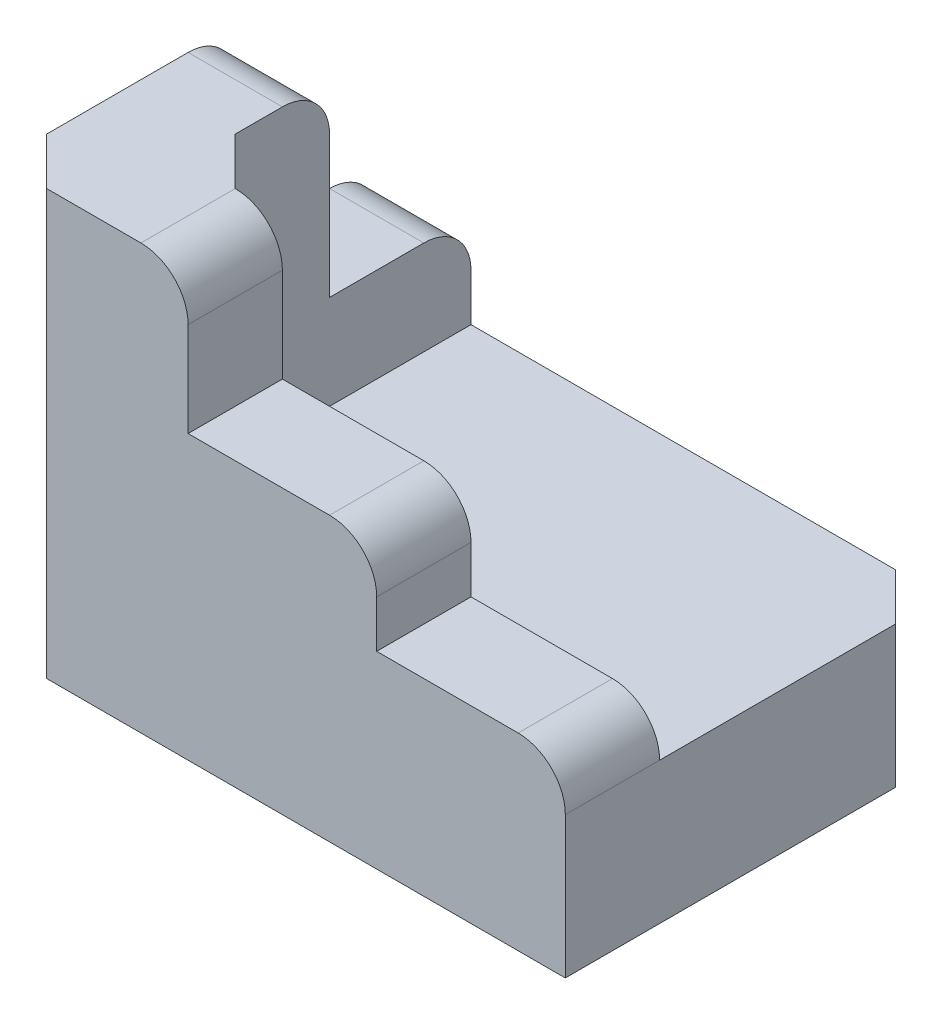
SolidWorks part; units mm, degrees
material "Cast Alloy Steel"
ref_plane "Front Plane" through (0, 0, 0) normal (0, 0, 1) x (1, 0, 0)
ref_plane "Top Plane" through (0, 0, 0) normal (0, 1, 0) x (1, 0, 0)
ref_plane "Right Plane" through (0, 0, 0) normal (1, 0, 0) x (0, 0, -1)
sketch "Sketch1" plane through (0, 0, 0) normal (0, 1, 0) x (1, 0, 0)
  line L1 (0, 0) -> (60, 0)
  line L2 (0, 0) -> (0, 40)
  line L3 (0, 40) -> (60, 40)
  line L4 (60, 0) -> (60, 40)
  line L5 (10, 40) -> (60, 40)
  line L6 (10, 40) -> (10, 10)
  line L7 (10, 10) -> (60, 10)
  line L8 (60, 40) -> (60, 10)
  dimension "D1" = 60
  dimension "D2" = 40
  dimension "D3" = 30
  dimension "D4" = 50
extrude "Boss-Extrude1" add sketch "Sketch1" along normal blind 45 contours L7 L6 L3 L2 L1 L4 | L6 L7 L4 L3 region at (0.7211, 0, -20) region at (35, 0, -25)
extrude "Cut-Extrude1" cut sketch "Sketch1<3>" against normal blind 30 from surface contours L5 L6 L7 L8 starting at face at (30, 45, -20)
sketch "Sketch1<3>" plane through (0, 0, 0) normal (0, 1, 0) x (1, 0, 0) same geometry as "Sketch1"
sketch "Sketch2" plane through (0, 0, 0) normal (0, 0, 1) x (1, 0, 0)
  line L0 (60, 45) -> (60, 0) construction
  line L1 (60, 45) -> (20, 45)
  line L2 (60, 45) -> (60, 30)
  line L3 (60, 30) -> (20, 30)
  line L4 (20, 45) -> (20, 30)
  line L5 (40, 30) -> (60, 30)
  line L6 (40, 30) -> (40, 20)
  line L7 (40, 20) -> (60, 20)
  line L8 (60, 30) -> (60, 20)
  point P10 (60, 25)
  dimension "D1" = 15
  dimension "D2" = 20
  dimension "D3" = 40
  dimension "D4" = 25
extrude "Cut-Extrude2" cut sketch "Sketch2" against normal blind 30 contours L1 L4 L3 L2 | L8 L3 L6 L7 region at (40, 37.5, 0) region at (50, 25, 0)
sketch "Sketch3" plane through (0, 0, 0) normal (1, 0, 0) x (0, 0, -1)
  line L1 (25, 45) -> (40, 45)
  line L2 (25, 45) -> (25, 25)
  line L3 (25, 25) -> (40, 25)
  line L4 (40, 45) -> (40, 25)
  point P4 (40, 45)
  dimension "D1" = 20
  dimension "D2" = 15
extrude "Cut-Extrude3" cut sketch "Sketch3" along normal blind 30
fillet "Fillet1" radius 5 5 edges at (5, 25, -40) (5, 45, -25) (20, 45, -5) (40, 30, -5) (60, 20, -5)
chamfer "Chamfer2" distance 5 angle 45 3 edges at (10, 30, -10) (60, 7.5, -40) (0, 22.5, 0)
